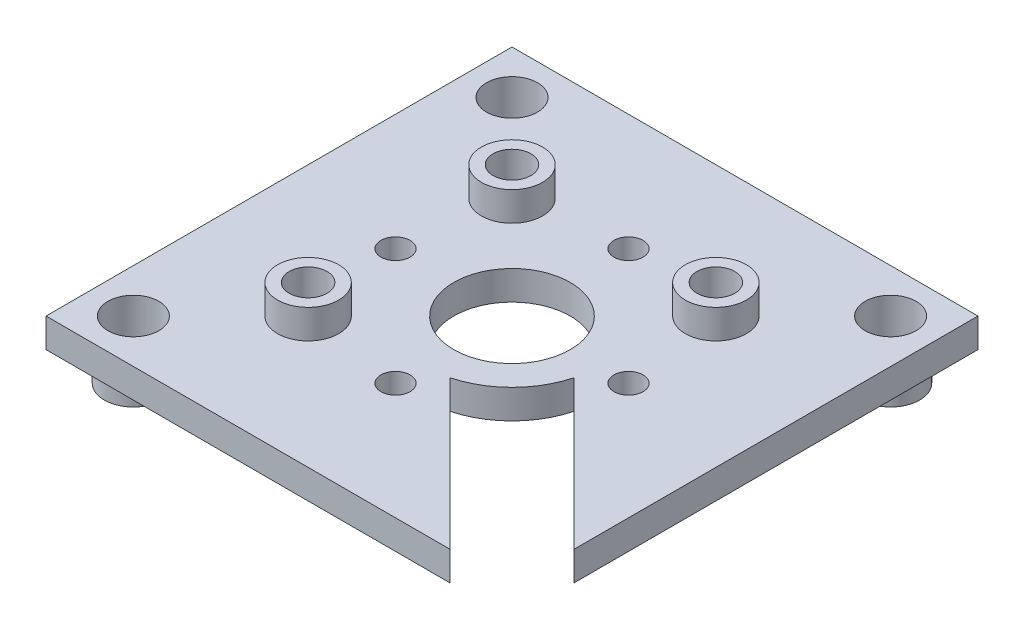
SolidWorks part; units mm, degrees
ref_plane "前视基准面" through (0, 0, 0) normal (0, 0, 1) x (1, 0, 0)
ref_plane "上视基准面" through (0, 0, 0) normal (0, 1, 0) x (1, 0, 0)
ref_plane "右视基准面" through (0, 0, 0) normal (1, 0, 0) x (0, 0, -1)
sketch "草图1" plane through (0, 0, 0) normal (0, 1, 0) x (1, 0, 0)
  line L0 (0, 0) -> (8, 0) construction
  line L1 (0, 0) -> (0, 8) construction
  line L3 (-16, 16) -> (16, 16)
  line L4 (-16, 16) -> (-16, -16)
  line L5 (-16, -16) -> (16, -16)
  line L6 (16, 16) -> (16, -16)
  circle A0 centre (0, 0) radius 8 construction
  circle A1 centre (8, 0) radius 1
  circle A2 centre (0, -8) radius 1
  circle A3 centre (-8, 0) radius 1
  circle A4 centre (0, 8) radius 1
  circle A5 centre (0, 0) radius 4
  circle A6 centre (0, 0) radius 16 construction
  circle A7 centre (13, 13) radius 1.75
  circle A8 centre (-13, 13) radius 1.75
  circle A9 centre (13, -13) radius 1.75
  circle A10 centre (-13, -13) radius 1.75
  dimension "D1" = 16
  dimension "D2" = 2
  dimension "D4" = 8
  dimension "D5" = 32
  dimension "D6" = 3.5
  dimension "D7" = 26
  dimension "D8" = 26
  dimension "D3" = 4
extrude "凸台-拉伸1" add sketch "草图1" along normal blind 2 contours L6 L3 L4 L5 A10 A8 A7 A5 A4 A3 A2 A1 A9 region at (0, 0, -15.5475)
sketch "草图2" plane through (0, 2, 0) normal (0, 1, 0) x (1, 0, 0)
  line L0 (0, 0) -> (7, 7) construction
  line L1 (0, 0) -> (9.8995, 0) construction
  line L2 (5.7956, -1.5529) -> (16, -11.7574)
  line L3 (16, 16) -> (16, -16) construction
  line L4 (0, 0) -> (16, -16) construction
  line L5 (1.5529, -5.7956) -> (11.7574, -16)
  line L6 (16, -11.7574) -> (16, -16)
  line L7 (16, -16) -> (11.7574, -16)
  circle A0 centre (0, 0) radius 9.8995 construction
  circle A1 centre (7, 7) radius 1.3
  circle A2 centre (7, 7) radius 2.1
  circle A3 centre (7, -7) radius 2.1
  circle A4 centre (7, -7) radius 1.3
  circle A5 centre (-7, -7) radius 2.1
  circle A6 centre (-7, -7) radius 1.3
  circle A7 centre (-7, 7) radius 2.1
  circle A8 centre (-7, 7) radius 1.3
  circle A9 centre (0, 0) radius 6 construction
  arc A10 (5.7956, -1.5529) -> (1.5529, -5.7956) centre (0, 0) cw
  line M20 (16, -16) -> (16, 16)
  line M23 (-16, -16) -> (16, -16)
  circle M24 centre (13, -13) radius 1.75
  dimension "D1" = 2.6
  dimension "D2" = 4.2
  dimension "D6" = 12
  dimension "D4" = 45
  dimension "D5" = 14
  dimension "D7" = 6
  dimension "D3" = 4
extrude "凸台-拉伸3" add sketch "草图2" along normal blind 2 contours A5 A6 | A7 A8 | A2 A1 region at (4.9594, 2, -7) region at (-9.0406, 2, 7) region at (-9.0406, 2, -7)
extrude "切除-拉伸2" cut sketch "草图2<6>" against normal up to surface (2 mm away) contours A8 | A6 | A1 | A3 A4 | A4 | L2 A10 L5 A3 M23 M20 M24 region at (9.5339, 2, 9.5339) region at (7, 2, -7) region at (4.9594, 2, 7) region at (7, 2, 7) region at (-7, 2, 7) region at (-7, 2, -7) up to face at (-13, 0, 14.75)
sketch "草图2<6>" plane through (0, 2, 0) normal (0, 1, 0) x (1, 0, 0) same geometry as "草图2"
sketch "草图3" plane through (0, 0, 0) normal (0, -1, 0) x (1, 0, 0)
  line L0 (0, 0) -> (3.1022, 0) construction
  line L1 (0, 0) -> (0, 3.2085) construction
  circle A0 centre (-13, 13) radius 1.75
  circle A1 centre (-13, 13) radius 2
  circle A2 centre (-13, 13) radius 1.75 construction
  circle A3 centre (-13, -13) radius 1.75
  circle A4 centre (-13, -13) radius 2
  circle A5 centre (13, -13) radius 1.75
  circle A6 centre (13, -13) radius 2
  dimension "D1" = 3.5
  dimension "D2" = 4
extrude "凸台-拉伸4" add sketch "草图3" along normal blind 2
